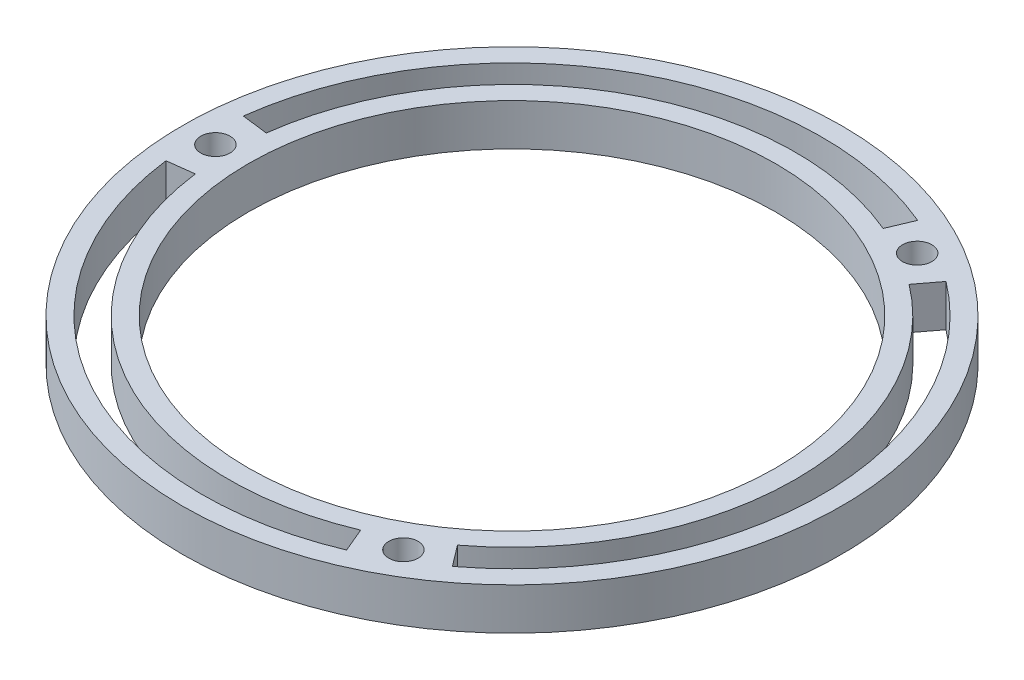
SolidWorks part; units mm, degrees
ref_plane "Front Plane" through (0, 0, 0) normal (0, 0, 1) x (1, 0, 0)
ref_plane "Top Plane" through (0, 0, 0) normal (0, 1, 0) x (1, 0, 0)
ref_plane "Right Plane" through (0, 0, 0) normal (1, 0, 0) x (0, 0, -1)
sketch "Sketch1" plane through (0, 0, 0) normal (0, 1, 0) x (1, 0, 0)
  line L0 (-50, 0) -> (50, 0) construction
  line L1 (-25, 43.3013) -> (25, -43.3013) construction
  line L2 (-25, -43.3013) -> (25, 43.3013) construction
  line L3 (30.2166, 39.8366) -> (24.1733, 31.8693)
  line L4 (19.3913, 46.0866) -> (15.513, 36.8693)
  line L5 (30.2166, -39.8366) -> (24.1733, -31.8693)
  line L6 (19.3913, -46.0866) -> (15.513, -36.8693)
  line L7 (-49.6078, 6.25) -> (-39.6863, 5)
  line L8 (-49.6078, -6.25) -> (-39.6863, -5)
  line L9 (0, 0) -> (15.513, 36.8693) construction
  line L10 (0, 0) -> (24.1733, 31.8693) construction
  line L11 (0, 0) -> (24.1733, -31.8693) construction
  line L12 (0, 0) -> (15.513, -36.8693) construction
  line L13 (0, 0) -> (-39.6863, 5) construction
  line L14 (-39.6863, -5) -> (0, 0) construction
  circle A0 centre (0, 0) radius 50
  circle A1 centre (0, 0) radius 47
  circle A2 centre (0, 0) radius 43
  circle A3 centre (0, 0) radius 40
  point P10 (0, 0)
  point P14 (0, 0)
  point P17 (0, 0)
  dimension "D1" = 100
  dimension "D2" = 3
  dimension "D5" = 60
  dimension "D6" = 60
  dimension "D7" = 5
  dimension "D8" = 5
  dimension "D9" = 5
  dimension "D10" = 5
  dimension "D11" = 5
  dimension "D12" = 5
  dimension "D3" = 4
  dimension "D4" = 3
extrude "Boss-Extrude1" add sketch "Sketch1" along normal blind 6.35 contours A1 L5 A0 L3 | A3 L5 A2 L3 | A3 L6 A2 L5 | A2 L6 A1 L5 | A1 L6 A0 L5 | A1 L8 A0 L6 | A3 L8 A2 L6 | A3 L7 A2 L8 | A2 L7 A1 L8 | A1 L7 A0 L8 | A1 L4 A0 L7 | A3 L4 A2 L7 | A3 L3 A2 L4 | A2 L3 A1 L4 | A1 L3 A0 L4 region at (44.0425, 0, -21.8721) region at (24.1943, 0, -41.9057) region at (22.4559, 0, -38.8948) region at (18.0546, 0, -45.0217) region at (37.876, 0, -18.8097) region at (20.7047, 0, -35.8617) region at (24.1943, 0, 41.9057) region at (-48.3886, 0, 0) region at (15.4453, 0, -38.5252) region at (22.4559, 0, 38.8948) region at (-44.9118, 0, 0) region at (-24.5905, 0, 42.592) region at (20.7047, 0, 35.8617) region at (-41.4095, 0, 0) region at (-21.1477, 0, 36.6289)
sketch "Sketch2" plane through (0, 6.35, 0) normal (0, 1, 0) x (1, 0, 0)
  line L1 (25, 43.3013) -> (20, 34.641) construction
  line L2 (20, -34.641) -> (25, -43.3013) construction
  line L3 (0, 0) -> (25.9863, -34.2595) construction
  line L4 (0, 0) -> (-40, 0) construction
  line L6 (0, 0) -> (20, -34.641) construction
  line L7 (-40, 0) -> (-50, 0) construction
  line L8 (0, 0) -> (20, 34.641) construction
  line L9 (0, 0) -> (16.6765, 39.6345) construction
  circle A0 centre (-45, 0) radius 2.225
  circle A1 centre (22.5, -38.9711) radius 2.225
  circle A2 centre (22.5, 38.9711) radius 2.225
  circle A3 centre (0, 0) radius 40 construction
  circle A4 centre (0, 0) radius 50 construction
  dimension "D1" = 4.45
  dimension "D2" = 5
  dimension "D3" = 5
extrude "M3-holes" cut sketch "Sketch2" against normal up to next
